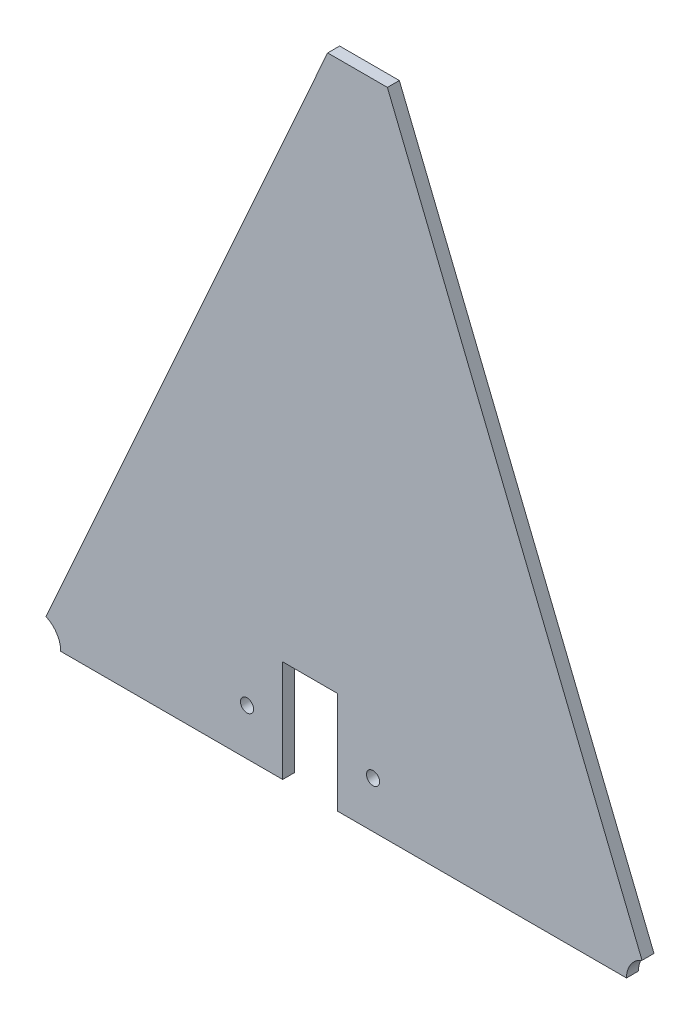
SolidWorks part; units mm, degrees
ref_plane "Front Plane" through (0, 0, 0) normal (0, 0, 1) x (1, 0, 0)
ref_plane "Top Plane" through (0, 0, 0) normal (0, 1, 0) x (1, 0, 0)
ref_plane "Right Plane" through (0, 0, 0) normal (1, 0, 0) x (0, 0, -1)
sketch "Sketch2" plane through (0, 0, 0) normal (0, 0, 1) x (1, 0, 0)
  line L0 (-189.7401, 245.3834) -> (-375.9085, -170.4146)
  line L1 (-375.9085, -170.4146) -> (16.7755, -170.4146)
  line L2 (16.7755, -170.4146) -> (-151.6401, 245.3834)
  line L4 (-189.7401, 245.3834) -> (-151.6401, 245.3834)
  dimension "D1" = 415.798
  dimension "D2" = 415.798
  dimension "D3" = 67.95
  dimension "D4" = 38.1
  dimension "D5" = 392.684
extrude "Boss-Extrude1" add sketch "Sketch2" along normal blind 7.62 contours L0 L1 L2 L4
sketch "Sketch5" plane through (0, 0, 0) normal (0, 0, -1) x (-1, 0, 0)
  circle A0 centre (375.9085, -170.4146) radius 15.875
  dimension "D1" = 31.75
extrude "Cut-Extrude2" cut sketch "Sketch5" against normal blind 50.8
sketch "Sketch6" plane through (0, 0, 0) normal (0, 0, -1) x (-1, 0, 0)
  circle A0 centre (-16.7755, -170.4146) radius 15.875
  dimension "D1" = 31.75
extrude "Cut-Extrude3" cut sketch "Sketch6" against normal blind 50.8 contours A0
ref_plane "Plane1" through (-360.0335, -170.4146, 0) normal (1, 0, 0) x (0, 0, -1)
sketch "Sketch8" plane through (0, 0, 0) normal (0, 0, -1) x (-1, 0, 0)
  line L0 (254.9716, -43.4146) -> (147.0216, -43.4146) construction
  line L1 (360.0335, -170.4146) -> (-0.9005, -170.4146) construction
  line L2 (254.9716, -170.4146) -> (254.9716, 97.7332) construction
  line L3 (254.9716, -43.4146) -> (254.9716, -170.4146) construction
  line L4 (147.0216, -43.4146) -> (147.0216, -170.4146) construction
  line L5 (147.0216, -170.4146) -> (183.5239, -170.4146) construction
  line L6 (183.5239, -170.4146) -> (183.5239, -105.3906) construction
  line L7 (170.6901, 245.3834) -> (179.5665, -170.4146) construction
  line L8 (189.7401, 245.3834) -> (151.6401, 245.3834) construction
  line L9 (183.5239, -105.3906) -> (218.4489, -105.3906) construction
  line L10 (218.4489, -105.3906) -> (218.4489, -170.4146) construction
  line L11 (218.4489, -170.4146) -> (218.4489, -105.3906)
  line L12 (218.4489, -105.3906) -> (183.5239, -105.3906)
  line L13 (183.5239, -105.3906) -> (183.5239, -170.4146)
  line L14 (153.8492, -170.4146) -> (153.8492, -48.647) construction
  dimension "D1" = 268.1478
  dimension "D2" = 107.95
  dimension "D3" = 127
  dimension "D4" = 36.5023
  dimension "D5" = 65.024
  dimension "D6" = 34.925
  dimension "D7" = 121.7676
extrude "Cut-Extrude4" cut sketch "Sketch8" against normal blind 7.62 and the other way through all contours L11 L12 L13
sketch "Sketch9" plane through (0, 0, 0) normal (0, 0, -1) x (-1, 0, 0)
  line L0 (164.9819, -140.8236) -> (183.5239, -140.8236) construction
  line L1 (183.5239, -170.4146) -> (183.5239, -105.3906) construction
  line L2 (160.7909, -145.0146) -> (160.7909, -170.4146) construction
  line L3 (183.5239, -170.4146) -> (-0.9005, -170.4146) construction
  line L4 (236.9909, -140.8236) -> (218.4489, -140.8236) construction
  line L5 (218.4489, -105.3906) -> (218.4489, -170.4146) construction
  line L6 (241.1819, -145.0146) -> (241.1819, -170.4146) construction
  line L7 (360.0335, -170.4146) -> (218.4489, -170.4146) construction
  circle A0 centre (160.7909, -140.8236) radius 4.191
  circle A1 centre (241.1819, -140.8236) radius 4.191
  dimension "D3" = 8.382
  dimension "D6" = 8.382
  dimension "D1" = 18.542
  dimension "D2" = 25.4
  dimension "D4" = 18.542
  dimension "D5" = 25.4
sketch "Sketch10" plane through (0, 0, 0) normal (0, 0, -1) x (-1, 0, 0)
  line L0 (218.4489, -110.7541) -> (349.1963, -110.7541) construction
  line L1 (218.4489, -105.3906) -> (218.4489, -170.4146) construction
  line L2 (189.7401, 245.3834) -> (369.4213, -155.9256) construction
  line L3 (7.3895, -110.7541) -> (138.1995, -110.7541) construction
  line L4 (-10.8158, -155.7008) -> (151.6401, 245.3834) construction
  dimension "D1" = 130.7473
  dimension "D2" = 130.81
extrude "Cut-Extrude6" cut sketch "Sketch9" against normal up to next
